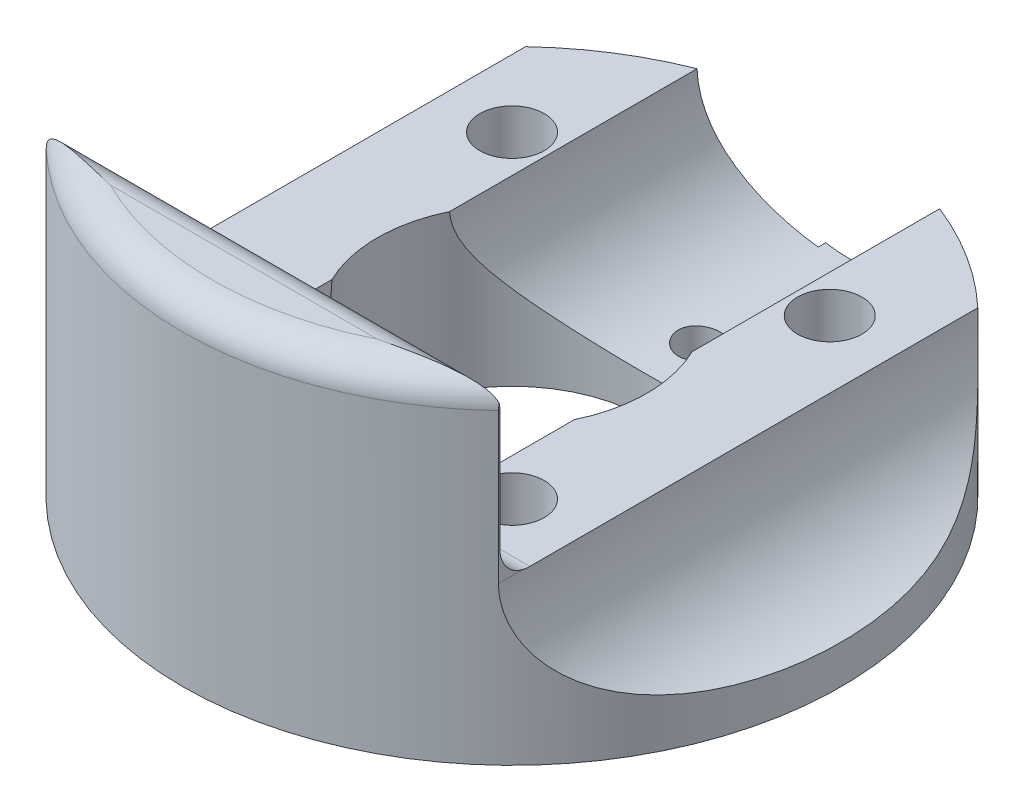
SolidWorks part; units mm, degrees
ref_plane "Front Plane" through (0, 0, 0) normal (0, 0, 1) x (1, 0, 0)
ref_plane "Top Plane" through (0, 0, 0) normal (0, 1, 0) x (1, 0, 0)
ref_plane "Right Plane" through (0, 0, 0) normal (1, 0, 0) x (0, 0, -1)
sketch "Sketch1" plane through (0, 0, 0) normal (0, 1, 0) x (1, 0, 0)
  line L0 (-1.5, 21.9488) -> (-1.5, 22.4488)
  line L1 (-1.5, 22.4488) -> (1.5, 22.4488)
  line L2 (1.5, 22.4488) -> (1.5, 21.9488)
  line L3 (0, 22.4488) -> (0, 0) construction
  arc A0 (-1.5, 21.9488) -> (1.5, 21.9488) centre (0, 0) ccw
  circle A1 centre (0, 0) radius 9
  dimension "D1" = 44
  dimension "D4" = 18
  dimension "D2" = 3
  dimension "D3" = 0.5
extrude "Boss-Extrude1" add sketch "Sketch1" along normal blind 2.5
sketch "Sketch2" plane through (0, 2.5, 0) normal (0, 1, 0) x (1, 0, 0)
  circle A0 centre (10.6066, 10.6066) radius 2 construction
  circle A1 centre (10.6066, -10.6066) radius 2 construction
  circle A2 centre (-10.6066, 10.6066) radius 2 construction
  circle A3 centre (-10.6066, -10.6066) radius 2 construction
  circle A4 centre (10.6066, 10.6066) radius 2 construction
  circle A5 centre (10.6066, -10.6066) radius 2 construction
  circle A6 centre (-10.6066, 10.6066) radius 2 construction
  circle A7 centre (-10.6066, -10.6066) radius 2 construction
  circle A8 centre (-10.6066, 10.6066) radius 2.15
  circle A9 centre (10.6066, 10.6066) radius 2.15
  circle A10 centre (10.6066, -10.6066) radius 2.15
  circle A11 centre (-10.6066, -10.6066) radius 2.15
  dimension "D1" = 4.3
extrude "Cut-Extrude1" cut sketch "Sketch2" against normal through all
sketch "Sketch3" plane through (0, 0, 0) normal (0, 0, 1) x (1, 0, 0)
  line L0 (0, 10.65) -> (-24.65, 10.65) construction
  line L1 (-15.0975, 10.45) -> (-8.0975, 10.45)
  line L2 (8.0975, 10.45) -> (15.0975, 10.45)
  line L3 (15.0975, 10.45) -> (15.0975, 2.5)
  line L4 (22, 2.5) -> (-22, 2.5) construction
  line L5 (15.0975, 2.5) -> (-15.0975, 2.5)
  line L6 (-8.4566, 2.5) -> (-12.7566, 2.5) construction
  line L7 (-15.0975, 2.5) -> (-15.0975, 10.45)
  line L8 (0, 10.65) -> (0, 0) construction
  line L9 (-22, 0) -> (22, 0) construction
  circle A1 centre (0, 10.65) radius 8 construction
  arc A2 (-8.0975, 10.45) -> (8.0975, 10.45) centre (0, 10.65) ccw
  dimension "D1" = 16
  dimension "D2" = 0.1
  dimension "D5" = 0.05
  dimension "D3" = 0.2
  dimension "D4" = 7
extrude "Boss-Extrude2" add sketch "Sketch3" along normal up to surface (15.9069 mm away) and the other way blind 25
sketch "Sketch4" plane through (0, 2.5, 0) normal (0, 1, 0) x (1, 0, 0)
  line L0 (-15.0975, -15.9069) -> (-15.0975, -16.002)
  line L1 (15.0975, -15.9069) -> (15.0975, -16.002)
  line L2 (-15.0975, -15.9069) -> (15.0975, -15.9069)
  arc A0 (-15.0975, 16.002) -> (15.0975, 16.002) centre (0, 0) ccw construction
  arc A1 (-15.0975, -16.002) -> (15.0975, -16.002) centre (0, 0) ccw
extrude "Boss-Extrude3" add sketch "Sketch4" along normal blind 20
sketch "Sketch5" plane through (0, 0, 0) normal (0, -1, 0) x (1, 0, 0)
  circle A0 centre (-10.6066, -10.6066) radius 2.15 construction
  circle A1 centre (10.6066, -10.6066) radius 2.15 construction
  circle A2 centre (10.6066, 10.6066) radius 2.15 construction
  circle A3 centre (-10.6066, 10.6066) radius 2.15 construction
  circle A4 centre (-10.6066, -10.6066) radius 2.15
  circle A5 centre (10.6066, -10.6066) radius 2.15
  circle A6 centre (10.6066, 10.6066) radius 2.15
  circle A7 centre (-10.6066, 10.6066) radius 2.15
extrude "Cut-Extrude2" cut sketch "Sketch5" against normal through all
sketch "Sketch6" plane through (0, 0, 0) normal (0, -1, 0) x (1, 0, 0)
  line L1 (-49.5569, 32.4518) -> (51.8766, 32.4518)
  line L2 (-49.5569, 32.4518) -> (-49.5569, -43.6058)
  line L3 (-1.5, -21.9488) -> (-1.5, -22.4488)
  line L4 (-1.5, -22.4488) -> (1.5, -22.4488)
  line L5 (1.5, -22.4488) -> (1.5, -21.9488)
  line L6 (-1.5, -21.9488) -> (-1.5, -22.4488)
  line L7 (-1.5, -22.4488) -> (1.5, -22.4488)
  line L8 (1.5, -22.4488) -> (1.5, -21.9488)
  line L9 (-49.5569, -43.6058) -> (51.8766, -43.6058)
  line L10 (51.8766, 32.4518) -> (51.8766, -43.6058)
  arc A1 (1.5, -21.9488) -> (-1.5, -21.9488) centre (0, 0) ccw
  arc A2 (1.5, -21.9488) -> (-1.5, -21.9488) centre (0, 0) ccw
  dimension "D1" = 0
extrude "Cut-Extrude3" cut sketch "Sketch6" against normal through all
sketch "Sketch7" plane through (0, 0, 0) normal (0, -1, 0) x (1, 0, 0)
  circle A0 centre (0, 0) radius 9 construction
  circle A1 centre (0, 0) radius 9
extrude "Cut-Extrude4" cut sketch "Sketch7" against normal through all
fillet "Fillet1" radius 8 2 edges at (15.0975, 2.5, 0) (-15.0975, 2.5, 0)
fillet "Fillet2" radius 2 2 edges at (0, 22.5, 22) (0, 22.5, 15.9069)
fillet "Fillet3" radius 2 2 edges at (-11.5976, 10.45, 15.9069) (11.5976, 10.45, 15.9069)
sketch "Sketch8" plane through (0, 0, 0) normal (0, -1, 0) x (1, 0, 0)
  line L0 (0, 12.5) -> (0, -12.5) construction
  circle A0 centre (0, 12.5) radius 1.4
  circle A1 centre (0, -12.5) radius 1.4
  dimension "D2" = 2.8
  dimension "D3" = 2.8
  dimension "D1" = 25
extrude "Cut-Extrude5" cut sketch "Sketch8" against normal through all
sketch "Sketch9" plane through (0, 0, 0) normal (0, -1, 0) x (1, 0, 0)
  line L0 (6.4723, -18.1576) -> (8.3768, -22.7807) construction
  line L1 (-8.3768, -22.7807) -> (-6.4723, -18.1576) construction
  line L2 (6.4723, -18.1576) -> (7.5107, -20.6782)
  line L3 (-7.5107, -20.6782) -> (-6.4723, -18.1576)
  line L4 (-2.5, -14.2856) -> (2.5, -14.2856) construction
  arc A0 (6.4723, -18.1576) -> (-6.4723, -18.1576) centre (0, -20.8239) ccw construction
  arc A1 (6.4723, -18.1576) -> (2.5, -14.2856) centre (0, -20.8239) ccw
  arc A2 (-7.5107, -20.6782) -> (7.5107, -20.6782) centre (0, 0) ccw
  arc A3 (1.5, -21.9488) -> (-1.5, -21.9488) centre (0, 0) ccw construction
  arc A4 (-2.5, -14.2856) -> (2.5, -14.2856) centre (0, -11.1631) ccw
  arc A5 (-2.5, -14.2856) -> (-6.4723, -18.1576) centre (0, -20.8239) ccw
  point P6 (-2.5, -14.2856)
  point P16 (2.5, -14.2856)
  point P17 (0, -11.6712)
  dimension "D1" = 5
  dimension "D2" = 4
extrude "Aligment feature" [suppressed] add sketch "Sketch9" along normal blind 2
